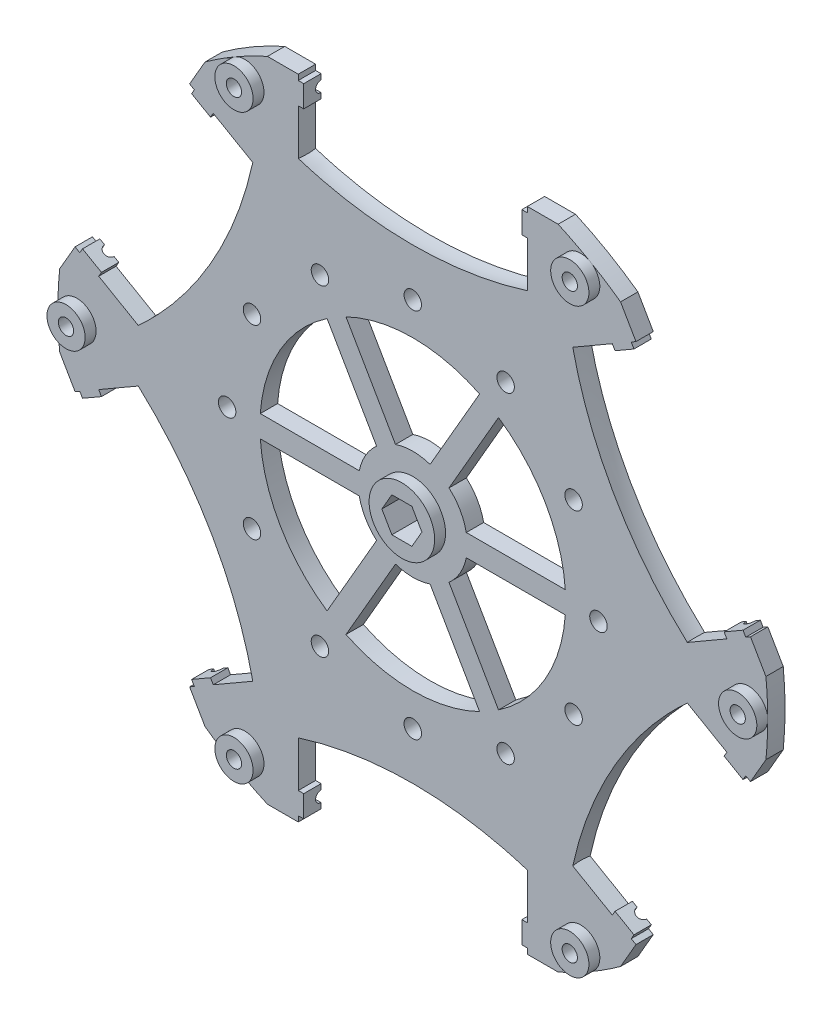
SolidWorks part; units mm, degrees
note: '?' marks a value the reader was unsure of.
material "Nylon 101"
ref_plane "Front Plane" through (0, 0, 0) normal (0, 0, 1) x (1, 0, 0)
ref_plane "Top Plane" through (0, 0, 0) normal (0, 1, 0) x (1, 0, 0)
ref_plane "Right Plane" through (0, 0, 0) normal (1, 0, 0) x (0, 0, -1)
ref_axis "Axis1" through (0, 0, 0) along (0, 0, 1)?
sketch "Master"
  line L0 (0, 69) -> (0, -69) construction
  line L1 (68.4737, 0) -> (34.2369, 59.3)
  line L2 (34.2369, 59.3) -> (-34.2369, 59.3)
  line L3 (-34.2369, 59.3) -> (-68.4737, 0)
  line L4 (-68.4737, 0) -> (-34.2369, -59.3)
  line L5 (-34.2369, -59.3) -> (34.2369, -59.3)
  line L6 (34.2369, -59.3) -> (68.4737, 0)
  line L7 (20.1736, 65.985) -> (20.1736, -65.985)
  line L8 (-20.1736, 65.985) -> (-20.1736, -65.985)
  line L9 (-20.1736, -65.985) -> (20.1736, 65.985) construction
  line L10 (-18.1736, 64.4881) -> (-18.1736, -64.4881)
  line L11 (18.1736, 64.4881) -> (18.1736, -64.4881)
  line L12 (-24.1736, 59.3) -> (-24.1736, -59.3)
  line L13 (24.1736, 59.3) -> (24.1736, -59.3)
  line L14 (-24.1736, 56.3) -> (24.1736, 56.3)
  line L15 (-24.1736, -56.3) -> (24.1736, -56.3)
  line L16 (-68.4737, 0) -> (68.4737, 0) construction
  line L17 (-24.1736, 57.2) -> (24.1736, 57.2)
  line L18 (-24.1736, 55.4) -> (24.1736, 55.4)
  line L19 (-24.1736, -55.4) -> (24.1736, -55.4)
  line L20 (-24.1736, -57.2) -> (24.1736, -57.2)
  line L21 (-24.1736, 57.3) -> (24.1736, 57.3)
  line L22 (-24.1736, 55.3) -> (24.1736, 55.3)
  line L23 (-24.1736, -55.3) -> (24.1736, -55.3)
  line L24 (-24.1736, -57.3) -> (24.1736, -57.3)
  line L25 (-24.1736, 57.2) -> (24.1736, 55.4) construction
  circle A0 centre (0, 0) radius 67
  circle A1 centre (0, 0) radius 59.3 construction
  circle A2 centre (0, 0) radius 69
  circle A3 centre (0, 0) radius 65
  point P12 (0, 0)
  point P18 (0, 0)
  point P21 (0, -67)
  point P22 (0, 67)
  point P24 (0, 67)
  point P25 (0, 67)
  point P29 (0, 67)
  point P48 (0, 0)
  point P66 (0, 0)
  point P74 (0, 0)
  dimension "D1" = 138
  dimension "D2" = 2
  dimension "D4" = 2
  dimension "D5" = 2
  dimension "D3" = 17
  dimension "D6" = 2
  dimension "D7" = 4
  dimension "D8" = 12.7
  dimension "D9" = 1.8
  dimension "D10" = 2
extrude "Boss-Extrude1" add sketch "Master" along normal mid plane 3.175
sketch "Sketch2" plane through (0, 0, 0) normal (0, 0, 1) x (1, 0, 0)
  line L0 (-20.9736, 56.3) -> (-20.9736, 66.784)
  line L2 (20.9736, 56.3) -> (20.9736, 66.784)
  line L3 (-20.1736, 65.985) -> (-20.1736, -65.985) construction
  line L4 (0, 69) -> (0, -69) construction
  line L5 (0, 69) -> (0, 56.3) construction
  line L6 (-24.1736, 56.3) -> (24.1736, 56.3) construction
  line L7 (-20.9736, 56.3) -> (20.9736, 56.3)
  arc A0 (20.9736, 66.784) -> (-20.9736, 66.784) centre (0, 0) ccw
  circle A2 centre (0, 0) radius 69 construction
  dimension "D1" = 0.8
  dimension "D2" = 1
revolve "Rollers" cut sketch "Sketch2" angle 360 about L7
sketch "Sketch1" plane through (0, 0, 1.5875) normal (0, 0, 1) x (1, 0, 0)
  line L0 (0, 69) -> (0, -69) construction
  line L1 (68.4737, 0) -> (34.2369, 59.3)
  line L2 (34.2369, 59.3) -> (-34.2369, 59.3)
  line L3 (-34.2369, 59.3) -> (-68.4737, 0)
  line L4 (-68.4737, 0) -> (-34.2369, -59.3)
  line L5 (-34.2369, -59.3) -> (34.2369, -59.3)
  line L6 (34.2369, -59.3) -> (68.4737, 0)
  line L7 (20.1736, 65.985) -> (20.1736, -65.985)
  line L8 (-20.1736, 65.985) -> (-20.1736, -65.985)
  line L9 (-20.1736, -65.985) -> (20.1736, 65.985) construction
  line L10 (-18.1736, 64.4881) -> (-18.1736, -64.4881)
  line L11 (18.1736, 64.4881) -> (18.1736, -64.4881)
  line L12 (-24.1736, 59.3) -> (-24.1736, -59.3)
  line L13 (24.1736, 59.3) -> (24.1736, -59.3)
  line L14 (-24.1736, 56.3) -> (24.1736, 56.3)
  line L15 (-24.1736, -56.3) -> (24.1736, -56.3)
  line L16 (-68.4737, 0) -> (68.4737, 0) construction
  line L17 (-24.1736, 57.2) -> (24.1736, 57.2)
  line L18 (-24.1736, 55.4) -> (24.1736, 55.4)
  line L19 (-24.1736, -55.4) -> (24.1736, -55.4)
  line L20 (-24.1736, -57.2) -> (24.1736, -57.2)
  line L21 (-24.1736, 57.3) -> (24.1736, 57.3)
  line L22 (-24.1736, 55.3) -> (24.1736, 55.3)
  line L23 (-24.1736, -55.3) -> (24.1736, -55.3)
  line L24 (-24.1736, -57.3) -> (24.1736, -57.3)
  line L25 (-24.1736, 57.2) -> (24.1736, 55.4) construction
  circle A0 centre (0, 0) radius 67
  circle A1 centre (0, 0) radius 59.3 construction
  circle A2 centre (0, 0) radius 69
  circle A3 centre (0, 0) radius 65
  point P12 (0, 0)
  point P18 (0, 0)
  point P21 (0, -67)
  point P22 (0, 67)
  point P24 (0, 67)
  point P25 (0, 67)
  point P29 (0, 67)
  point P48 (0, 0)
  point P66 (0, 0)
  point P74 (0, 0)
extrude "Cut-Extrude1" cut sketch "Sketch1" against normal through all both and the other way through all flip side to cut
sketch "Sketch4" plane through (0, 0, 0) normal (0, 0, 1) x (1, 0, 0)
  line L0 (-28, 0) -> (28, 0) construction
  line L1 (-14, -24.2487) -> (14, 24.2487) construction
  line L2 (14, -24.2487) -> (-14, 24.2487) construction
  line L3 (-27.9285, 2) -> (27.9285, 2)
  line L4 (-27.9285, -2) -> (27.9285, -2)
  line L5 (-12.2322, 25.1868) -> (15.6963, -23.1868)
  line L6 (-15.6963, 23.1868) -> (12.2322, -25.1868)
  line L7 (-12.2322, -25.1868) -> (15.6963, 23.1868)
  line L8 (-15.6963, -23.1868) -> (12.2322, 25.1868)
  circle A0 centre (0, 0) radius 29
  circle A1 centre (0, 0) radius 28
  point P3 (0, 0)
  point P6 (0, 0)
  point P9 (0, 0)
  point P20 (0, 0)
  dimension "D1" = 56
  dimension "D2" = 4
  dimension "D3" = 4
  dimension "D4" = 4
  dimension "D5" = 60
  dimension "D6" = 60
  dimension "D7" = 1
extrude "Spokes" cut sketch "Sketch4" along normal through all both and the other way through all contours A1
sketch "Sketch5" plane through (0, 0, 0) normal (0, 0, 1) x (1, 0, 0)
  line L0 (-28, 0) -> (28, 0) construction
  line L1 (-14, -24.2487) -> (14, 24.2487) construction
  line L2 (14, -24.2487) -> (-14, 24.2487) construction
  line L3 (-27.9285, 2) -> (27.9285, 2)
  line L4 (-27.9285, -2) -> (27.9285, -2)
  line L5 (-12.2322, 25.1868) -> (15.6963, -23.1868)
  line L6 (-15.6963, 23.1868) -> (12.2322, -25.1868)
  line L7 (-12.2322, -25.1868) -> (15.6963, 23.1868)
  line L8 (-15.6963, -23.1868) -> (12.2322, 25.1868)
  line L9 (-27.9285, -2) -> (27.9285, -2) construction
  circle A0 centre (0, 0) radius 29
  circle A1 centre (0, 0) radius 28
  circle A2 centre (0, 0) radius 28 construction
  point P3 (0, 0)
  point P6 (0, 0)
  point P9 (0, 0)
  point P20 (0, 0)
extrude "Boss-Extrude5" add sketch "Sketch5" along normal mid plane 3.175 contours L8 A1 L7 L6 L4 | L7 A1 L8 L5 L3 | L4 A1 L3 L7 L5 | L6 A1 L5 L4 L7 | L3 A1 L4 L8 L6 | L8 L4 L6 | L6 L7 L4 | L7 L4 L5 | L5 L7 L3 | L5 A1 L6 L3 L8 | L8 L3 L5 | L6 L8 L3 | L8 L6 L4 L7 L5 L3
sketch "Axle" plane through (0, 0, 0) normal (0, 0, 1) x (1, 0, 0)
  line L1 (3.6662, 0) -> (1.8331, 3.175)
  line L2 (1.8331, 3.175) -> (-1.8331, 3.175)
  line L3 (-1.8331, 3.175) -> (-3.6662, 0)
  line L4 (-3.6662, 0) -> (-1.8331, -3.175)
  line L5 (-1.8331, -3.175) -> (1.8331, -3.175)
  line L6 (1.8331, -3.175) -> (3.6662, 0)
  line L7 (0, 0) -> (0, 10) construction
  line L8 (0, 0) -> (1.8331, 3.175) construction
  circle A0 centre (0, 0) radius 10
  circle A1 centre (0, 0) radius 3.175 construction
  dimension "D1" = 20
  dimension "D2" = 6.35
  dimension "D3" = 30
extrude "Hub" add sketch "Axle" along normal mid plane 3.175
sketch "Sketch9" plane through (0, 0, 0) normal (0, 0, 1) x (1, 0, 0)
  line L1 (3.6662, 0) -> (1.8331, 3.175)
  line L2 (1.8331, 3.175) -> (-1.8331, 3.175)
  line L3 (-1.8331, 3.175) -> (-3.6662, 0)
  line L4 (-3.6662, 0) -> (-1.8331, -3.175)
  line L5 (-1.8331, -3.175) -> (1.8331, -3.175)
  line L6 (1.8331, -3.175) -> (3.6662, 0)
  line L7 (0, 0) -> (0, 10) construction
  line L8 (0, 0) -> (1.8331, 3.175) construction
  circle A0 centre (0, 0) radius 10
  circle A1 centre (0, 0) radius 3.175 construction
extrude "Hex axle" cut sketch "Sketch9" along normal through all both and the other way through all contours L5 L6 L1 L2 L3 L4
pattern_circular "CirPattern2" count 6 over 360 about axis through (0, 0, 0) along (0, 0, 1) of "Rollers"
sketch "Sketch12" plane through (0, 0, 0) normal (1, 0, 0) x (0, 0, -1)
  line L0 (1.5875, 57.3) -> (1.5875, 55.3)
  line L1 (1.5875, 45.9369) -> (1.5875, 59.3) construction
  line L2 (1.5875, 45.9369) -> (1.5875, 59.3) construction
  line L3 (0, 57.2) -> (0, 55.4) construction
  line L4 (0, 57.2) -> (0, 55.4) construction
  line L5 (1.5875, 56.3) -> (-1.5875, 56.3) construction
  line L6 (-1.5875, 59.3) -> (-1.5875, 52.7017) construction
  arc A1 (1.5875, 57.3) -> (1.5875, 55.3) centre (1.5875, 56.3) ccw
  point P7 (0, 56.3)
  dimension "D1" = 2
sketch "Sketch17" plane through (0, 0, 1.5875) normal (0, 0, 1) x (1, 0, 0)
  line L0 (-20.9736, 45.9369) -> (-20.9736, 59.3) construction
  line L1 (-20.9736, 54.3) -> (-20.9736, 58.3)
  line L2 (-20.9736, 58.3) -> (-19.9736, 58.3)
  line L3 (-19.9736, 58.3) -> (-19.9736, 54.3)
  line L4 (-19.9736, 54.3) -> (-20.9736, 54.3)
  line L6 (-24.1736, 56.3) -> (24.1736, 56.3) construction
  line L7 (20.9736, 59.3) -> (20.9736, 45.9369) construction
  line L8 (20.9736, 58.3) -> (20.9736, 54.3)
  line L9 (20.9736, 58.3) -> (19.9736, 58.3)
  line L10 (19.9736, 58.3) -> (19.9736, 54.3)
  line L11 (19.9736, 54.3) -> (20.9736, 54.3)
  point P4 (-19.9736, 56.3)
  dimension "D1" = 4
  dimension "D2" = 1
extrude "Roller insets" add sketch "Sketch17" against normal through all
pattern_circular "CirPattern8" count 6 over 360 about axis through (0, 0, 0) along (0, 0, 1) of "Roller insets"
sketch "Screw Holes"
  line L0 (-68.4737, 0) -> (68.4737, 0) construction
  circle A0 centre (34, 0) radius 1.6
  dimension "D1" = 3.2
  dimension "D2" = 34
extrude "Disk spacers" cut sketch "Screw Holes" against normal through all both and the other way through all
pattern_circular "CirPattern3" count 12 over 360 about axis through (0, 0, 0) along (0, 0, 1) of "Disk spacers"
sketch "Sketch10" plane through (0, 0, 1.5875) normal (0, 0, 1) x (1, 0, 0)
  line L0 (1.8331, -3.175) -> (3.6662, 0) construction
  line L1 (1.8331, -3.175) -> (3.6662, 0)
  line L2 (-1.8331, -3.175) -> (1.8331, -3.175) construction
  line L3 (-1.8331, -3.175) -> (1.8331, -3.175)
  line L4 (-3.6662, 0) -> (-1.8331, -3.175) construction
  line L5 (-3.6662, 0) -> (-1.8331, -3.175)
  line L6 (-1.8331, 3.175) -> (-3.6662, 0) construction
  line L7 (-1.8331, 3.175) -> (-3.6662, 0)
  line L8 (1.8331, 3.175) -> (-1.8331, 3.175) construction
  line L9 (1.8331, 3.175) -> (-1.8331, 3.175)
  line L10 (3.6662, 0) -> (1.8331, 3.175) construction
  line L11 (3.6662, 0) -> (1.8331, 3.175)
  circle A0 centre (0, 0) radius 6
  dimension "D1" = 12
extrude "Hub spacer inner" add sketch "Sketch10" along normal blind 2
sketch "Sketch11" [suppressed] plane through (0, 0, 1.5) normal (0, 0, 1) x (1, 0, 0)
  line L0 (0, -3.6662) -> (3.175, -1.8331) construction
  line L1 (0, -3.6662) -> (3.175, -1.8331)
  line L2 (-3.175, -1.8331) -> (0, -3.6662) construction
  line L3 (-3.175, -1.8331) -> (0, -3.6662)
  line L4 (0, 3.6662) -> (-3.175, 1.8331) construction
  line L5 (0, 3.6662) -> (-3.175, 1.8331)
  line L6 (3.175, 1.8331) -> (0, 3.6662) construction
  line L7 (3.175, 1.8331) -> (0, 3.6662)
  line L8 (3.175, -1.8331) -> (3.175, 1.8331) construction
  line L9 (3.175, -1.8331) -> (3.175, 1.8331)
  line L10 (-3.175, 1.8331) -> (-3.175, -1.8331) construction
  line L11 (-3.175, 1.8331) -> (-3.175, -1.8331)
  circle A0 centre (0, 0) radius 6
  dimension "D1" = 12
extrude "Hub spacer outer" [suppressed] add sketch "Sketch11" along normal blind 2
extrude "Roller axles" cut sketch "Sketch12" against normal mid plane 50.4
pattern_circular "CirPattern4" count 6 over 360 about axis through (0, 0, 0) along (0, 0, 1) of "Roller axles"
sketch "Sketch13" plane through (0, 0, 0) normal (1, 0, 0) x (0, 0, -1)
  line L0 (-1.5875, 45.9369) -> (-1.5875, 54.3) construction
  line L1 (-1.5875, 45.9369) -> (-1.5875, 54.3) construction
  line L2 (0, 57.2) -> (0, 55.4) construction
  line L3 (0, 57.2) -> (0, 55.4) construction
  line L4 (-1.5875, 56.3) -> (1.5875, 56.3) construction
  line L5 (1.5875, 52.7017) -> (1.5875, 59.3) construction
  circle A0 centre (-1.5875, 56.3) radius 1.2
  point P6 (0, 56.3)
  dimension "D1" = 2.4
extrude "Roller axles hub-side" [suppressed] cut sketch "Sketch13" against normal mid plane 50.4
pattern_circular "CirPattern5" [suppressed] count 6 over 360 about axis through (0, 0, 0) along (0, 0, 1)
sketch "Sketch15" plane through (0, 0, 0) normal (0, 0, 1) x (1, 0, 0)
  line L0 (0, 0) -> (17, 29.4449) construction
  line L1 (17, 29.4449) -> (32.5, 56.2917) construction
  arc A1 (38.0464, 52.7017) -> (26.6179, 59.3) centre (0, 0) ccw construction
  circle A2 centre (30.75, 53.2606) radius 1.4
  circle A3 centre (30.75, 53.2606) radius 3.5 construction
  dimension "D1" = 2.8
  dimension "D2" = 7
extrude "Disk screws" cut sketch "Sketch15" against normal through all both and the other way through all
pattern_circular "CirPattern6" count 6 over 360 about axis through (0, 0, 0) along (0, 0, 1) of "Disk screws"
sketch "Sketch16" plane through (0, 0, 1.5875) normal (0, 0, 1) x (1, 0, 0)
  circle A3 centre (30.75, 53.2606) radius 3.5 construction
  circle A4 centre (30.75, 53.2606) radius 3.5
  circle A5 centre (30.75, 53.2606) radius 1.4 construction
  circle A6 centre (30.75, 53.2606) radius 1.4
extrude "Disk screws boss" add sketch "Sketch16" along normal blind 2
pattern_circular "CirPattern7" count 6 over 360 about axis through (0, 0, 0) along (0, 0, 1) of "Disk screws boss"
equation "\"hub_thickness\"= 25.4 / 8"
equation "\"D1@Boss-Extrude1\"=\"hub_thickness\""
equation "\"D1\"= \"hub_thickness\""
equation "\"spoke_width\"=4"
equation "\"D2@Sketch4\" = \"spoke_width\""
equation "\"D3@Sketch4\" = \"spoke_width\""
equation "\"D4@Sketch4\" = \"spoke_width\""
equation "\"D1@Boss-Extrude5\"=\"hub_thickness\""
equation "\"roller_axle_dia\"= 2.4"
equation "\"roller_axle_len\"= 50.4"
equation "\"D1@Roller axles\"=\"roller_axle_len\""
equation "\"D1@Hub\"=\"hub_thickness\""
equation "\"D1@Sketch13\"=\"roller_axle_dia\""
equation "\"D1@Roller axles hub-side\" = \"roller_axle_len\""
